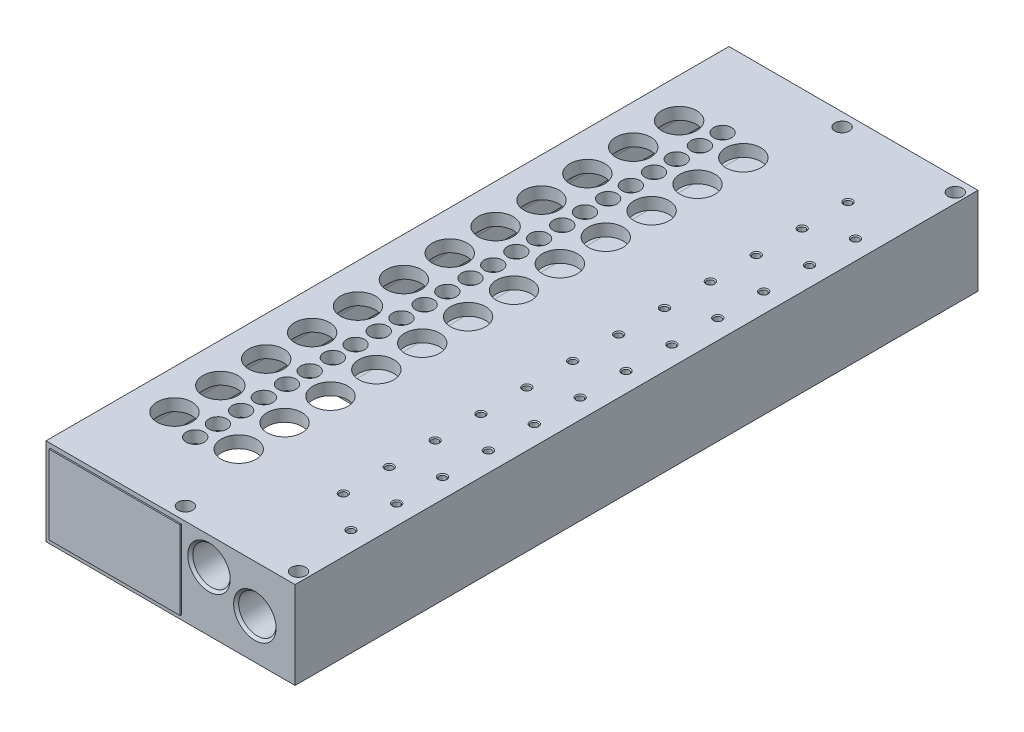
SolidWorks part; units mm, degrees
ref_plane "Front Plane" through (0, 0, 0) normal (0, 0, 1) x (1, 0, 0)
ref_plane "Top Plane" through (0, 0, 0) normal (0, 1, 0) x (1, 0, 0)
ref_plane "Right Plane" through (0, 0, 0) normal (1, 0, 0) x (0, 0, -1)
ref_plane "Plane1" through (0, 0, -135.9) normal (0, 0, 1) x (1, 0, 0)
sketch "Sketch1" plane through (0, 0, -135.9) normal (0, 0, 1) x (1, 0, 0)
  line L0 (0, 20) -> (0, 0)
  line L1 (0, 0) -> (57, 0)
  line L2 (57, 0) -> (57, 20)
  line L3 (57, 20) -> (0, 20)
  line L4 (46.9, 7.1004) -> (46.9, 8.5)
  line L5 (47.4, 9) -> (47.85, 9)
  line L6 (48.35, 9.5) -> (48.35, 11.3964)
  line L7 (38.7, 10.8091) -> (38.7, 15.1909)
  line L8 (2.5, 11.35) -> (2.5, 9.25)
  line L9 (2.5, 9.25) -> (4, 9.25)
  line L10 (4, 9.25) -> (4, 4.75)
  line L11 (6, 2.75) -> (26.7, 2.75)
  line L12 (28.7, 4.75) -> (28.7, 9.25)
  line L13 (28.7, 9.25) -> (30.2, 9.25)
  line L14 (30.2, 9.25) -> (30.2, 11.35)
  line L15 (30.2, 11.35) -> (28.7, 11.35)
  line L16 (28.7, 11.35) -> (28.7, 15.25)
  line L17 (26.7, 17.25) -> (6, 17.25)
  line L18 (4, 15.25) -> (4, 11.35)
  line L19 (4, 11.35) -> (2.5, 11.35)
  arc A0 (46.7429, 12.8926) -> (46.9, 7.1004) centre (46.95, 10) ccw
  arc A1 (46.9, 8.5) -> (47.4, 9) centre (47.4, 8.5) cw
  arc A2 (47.85, 9) -> (48.35, 9.5) centre (47.85, 9.5) ccw
  arc A3 (48.35, 11.3964) -> (46.7429, 12.8926) centre (46.85, 11.3964) ccw
  arc A4 (38.7, 15.1909) -> (38.7, 10.8091) centre (36.8, 13) ccw
  arc A5 (4, 4.75) -> (6, 2.75) centre (6, 4.75) ccw
  arc A6 (26.7, 2.75) -> (28.7, 4.75) centre (26.7, 4.75) ccw
  arc A7 (28.7, 15.25) -> (26.7, 17.25) centre (26.7, 15.25) ccw
  arc A8 (6, 17.25) -> (4, 15.25) centre (6, 15.25) ccw
extrude "Boss-Extrude1" add sketch "Sketch1" along normal blind 156.3
ref_plane "Plane2" through (0, 20, 0) normal (0, 1, 0) x (1, 0, 0)
sketch "Sketch2" plane through (0, 20, 0) normal (0, 1, 0) x (1, 0, 0)
  circle A0 centre (9, 0) radius 4
extrude "Cut-Extrude1" cut sketch "Sketch2" against normal blind 3
ref_plane "Plane3" through (0, 20, 0) normal (0, 1, 0) x (1, 0, 0)
sketch "Sketch3" plane through (0, 20, 0) normal (0, 1, 0) x (1, 0, 0)
  circle A0 centre (9, 10.5) radius 4
extrude "Cut-Extrude2" cut sketch "Sketch3" against normal blind 3
ref_plane "Plane4" through (0, 20, 0) normal (0, 1, 0) x (1, 0, 0)
sketch "Sketch4" plane through (0, 20, 0) normal (0, 1, 0) x (1, 0, 0)
  circle A0 centre (9, 21) radius 4
extrude "Cut-Extrude3" cut sketch "Sketch4" against normal blind 3
ref_plane "Plane5" through (0, 20, 0) normal (0, 1, 0) x (1, 0, 0)
sketch "Sketch5" plane through (0, 20, 0) normal (0, 1, 0) x (1, 0, 0)
  circle A0 centre (9, 31.5) radius 4
extrude "Cut-Extrude4" cut sketch "Sketch5" against normal blind 3
ref_plane "Plane6" through (0, 20, 0) normal (0, 1, 0) x (1, 0, 0)
sketch "Sketch6" plane through (0, 20, 0) normal (0, 1, 0) x (1, 0, 0)
  circle A0 centre (9, 42) radius 4
extrude "Cut-Extrude5" cut sketch "Sketch6" against normal blind 3
ref_plane "Plane7" through (0, 20, 0) normal (0, 1, 0) x (1, 0, 0)
sketch "Sketch7" plane through (0, 20, 0) normal (0, 1, 0) x (1, 0, 0)
  circle A0 centre (9, 52.5) radius 4
extrude "Cut-Extrude6" cut sketch "Sketch7" against normal blind 3
ref_plane "Plane8" through (0, 20, 0) normal (0, 1, 0) x (1, 0, 0)
sketch "Sketch8" plane through (0, 20, 0) normal (0, 1, 0) x (1, 0, 0)
  circle A0 centre (9, 63) radius 4
extrude "Cut-Extrude7" cut sketch "Sketch8" against normal blind 3
ref_plane "Plane9" through (0, 20, 0) normal (0, 1, 0) x (1, 0, 0)
sketch "Sketch9" plane through (0, 20, 0) normal (0, 1, 0) x (1, 0, 0)
  circle A0 centre (9, 73.5) radius 4
extrude "Cut-Extrude8" cut sketch "Sketch9" against normal blind 3
ref_plane "Plane10" through (0, 20, 0) normal (0, 1, 0) x (1, 0, 0)
sketch "Sketch10" plane through (0, 20, 0) normal (0, 1, 0) x (1, 0, 0)
  circle A0 centre (9, 84) radius 4
extrude "Cut-Extrude9" cut sketch "Sketch10" against normal blind 3
ref_plane "Plane11" through (0, 20, 0) normal (0, 1, 0) x (1, 0, 0)
sketch "Sketch11" plane through (0, 20, 0) normal (0, 1, 0) x (1, 0, 0)
  circle A0 centre (9, 94.5) radius 4
extrude "Cut-Extrude10" cut sketch "Sketch11" against normal blind 3
ref_plane "Plane12" through (0, 20, 0) normal (0, 1, 0) x (1, 0, 0)
sketch "Sketch12" plane through (0, 20, 0) normal (0, 1, 0) x (1, 0, 0)
  circle A0 centre (9, 105) radius 4
extrude "Cut-Extrude11" cut sketch "Sketch12" against normal blind 3
ref_plane "Plane13" through (0, 20, 0) normal (0, 1, 0) x (1, 0, 0)
sketch "Sketch13" plane through (0, 20, 0) normal (0, 1, 0) x (1, 0, 0)
  circle A0 centre (9, 115.5) radius 4
extrude "Cut-Extrude12" cut sketch "Sketch13" against normal blind 3
ref_plane "Plane14" through (0, 20, 0) normal (0, 1, 0) x (1, 0, 0)
sketch "Sketch14" plane through (0, 20, 0) normal (0, 1, 0) x (1, 0, 0)
  circle A0 centre (23.7, 0) radius 4
extrude "Cut-Extrude13" cut sketch "Sketch14" against normal blind 3
ref_plane "Plane15" through (0, 20, 0) normal (0, 1, 0) x (1, 0, 0)
sketch "Sketch15" plane through (0, 20, 0) normal (0, 1, 0) x (1, 0, 0)
  circle A0 centre (23.7, 10.5) radius 4
extrude "Cut-Extrude14" cut sketch "Sketch15" against normal blind 3
ref_plane "Plane16" through (0, 20, 0) normal (0, 1, 0) x (1, 0, 0)
sketch "Sketch16" plane through (0, 20, 0) normal (0, 1, 0) x (1, 0, 0)
  circle A0 centre (23.7, 21) radius 4
extrude "Cut-Extrude15" cut sketch "Sketch16" against normal blind 3
ref_plane "Plane17" through (0, 20, 0) normal (0, 1, 0) x (1, 0, 0)
sketch "Sketch17" plane through (0, 20, 0) normal (0, 1, 0) x (1, 0, 0)
  circle A0 centre (23.7, 31.5) radius 4
extrude "Cut-Extrude16" cut sketch "Sketch17" against normal blind 3
ref_plane "Plane18" through (0, 20, 0) normal (0, 1, 0) x (1, 0, 0)
sketch "Sketch18" plane through (0, 20, 0) normal (0, 1, 0) x (1, 0, 0)
  circle A0 centre (23.7, 42) radius 4
extrude "Cut-Extrude17" cut sketch "Sketch18" against normal blind 3
ref_plane "Plane19" through (0, 20, 0) normal (0, 1, 0) x (1, 0, 0)
sketch "Sketch19" plane through (0, 20, 0) normal (0, 1, 0) x (1, 0, 0)
  circle A0 centre (23.7, 52.5) radius 4
extrude "Cut-Extrude18" cut sketch "Sketch19" against normal blind 3
ref_plane "Plane20" through (0, 20, 0) normal (0, 1, 0) x (1, 0, 0)
sketch "Sketch20" plane through (0, 20, 0) normal (0, 1, 0) x (1, 0, 0)
  circle A0 centre (23.7, 63) radius 4
extrude "Cut-Extrude19" cut sketch "Sketch20" against normal blind 3
ref_plane "Plane21" through (0, 20, 0) normal (0, 1, 0) x (1, 0, 0)
sketch "Sketch21" plane through (0, 20, 0) normal (0, 1, 0) x (1, 0, 0)
  circle A0 centre (23.7, 73.5) radius 4
extrude "Cut-Extrude20" cut sketch "Sketch21" against normal blind 3
ref_plane "Plane22" through (0, 20, 0) normal (0, 1, 0) x (1, 0, 0)
sketch "Sketch22" plane through (0, 20, 0) normal (0, 1, 0) x (1, 0, 0)
  circle A0 centre (23.7, 84) radius 4
extrude "Cut-Extrude21" cut sketch "Sketch22" against normal blind 3
ref_plane "Plane23" through (0, 20, 0) normal (0, 1, 0) x (1, 0, 0)
sketch "Sketch23" plane through (0, 20, 0) normal (0, 1, 0) x (1, 0, 0)
  circle A0 centre (23.7, 94.5) radius 4
extrude "Cut-Extrude22" cut sketch "Sketch23" against normal blind 3
ref_plane "Plane24" through (0, 20, 0) normal (0, 1, 0) x (1, 0, 0)
sketch "Sketch24" plane through (0, 20, 0) normal (0, 1, 0) x (1, 0, 0)
  circle A0 centre (23.7, 105) radius 4
extrude "Cut-Extrude23" cut sketch "Sketch24" against normal blind 3
ref_plane "Plane25" through (0, 20, 0) normal (0, 1, 0) x (1, 0, 0)
sketch "Sketch25" plane through (0, 20, 0) normal (0, 1, 0) x (1, 0, 0)
  circle A0 centre (23.7, 115.5) radius 4
extrude "Cut-Extrude24" cut sketch "Sketch25" against normal blind 3
ref_plane "Plane26" through (0, 20, 0) normal (0, 1, 0) x (1, 0, 0)
sketch "Sketch26" plane through (0, 20, 0) normal (0, 1, 0) x (1, 0, 0)
  circle A0 centre (16.35, -2.6) radius 2.05
extrude "Cut-Extrude25" cut sketch "Sketch26" against normal blind 3
ref_plane "Plane27" through (0, 20, 0) normal (0, 1, 0) x (1, 0, 0)
sketch "Sketch27" plane through (0, 20, 0) normal (0, 1, 0) x (1, 0, 0)
  circle A0 centre (16.35, 7.9) radius 2.05
extrude "Cut-Extrude26" cut sketch "Sketch27" against normal blind 3
ref_plane "Plane28" through (0, 20, 0) normal (0, 1, 0) x (1, 0, 0)
sketch "Sketch28" plane through (0, 20, 0) normal (0, 1, 0) x (1, 0, 0)
  circle A0 centre (16.35, 18.4) radius 2.05
extrude "Cut-Extrude27" cut sketch "Sketch28" against normal blind 3
ref_plane "Plane29" through (0, 20, 0) normal (0, 1, 0) x (1, 0, 0)
sketch "Sketch29" plane through (0, 20, 0) normal (0, 1, 0) x (1, 0, 0)
  circle A0 centre (16.35, 28.9) radius 2.05
extrude "Cut-Extrude28" cut sketch "Sketch29" against normal blind 3
ref_plane "Plane30" through (0, 20, 0) normal (0, 1, 0) x (1, 0, 0)
sketch "Sketch30" plane through (0, 20, 0) normal (0, 1, 0) x (1, 0, 0)
  circle A0 centre (16.35, 39.4) radius 2.05
extrude "Cut-Extrude29" cut sketch "Sketch30" against normal blind 3
ref_plane "Plane31" through (0, 20, 0) normal (0, 1, 0) x (1, 0, 0)
sketch "Sketch31" plane through (0, 20, 0) normal (0, 1, 0) x (1, 0, 0)
  circle A0 centre (16.35, 49.9) radius 2.05
extrude "Cut-Extrude30" cut sketch "Sketch31" against normal blind 3
ref_plane "Plane32" through (0, 20, 0) normal (0, 1, 0) x (1, 0, 0)
sketch "Sketch32" plane through (0, 20, 0) normal (0, 1, 0) x (1, 0, 0)
  circle A0 centre (16.35, 60.4) radius 2.05
extrude "Cut-Extrude31" cut sketch "Sketch32" against normal blind 3
ref_plane "Plane33" through (0, 20, 0) normal (0, 1, 0) x (1, 0, 0)
sketch "Sketch33" plane through (0, 20, 0) normal (0, 1, 0) x (1, 0, 0)
  circle A0 centre (16.35, 70.9) radius 2.05
extrude "Cut-Extrude32" cut sketch "Sketch33" against normal blind 3
ref_plane "Plane34" through (0, 20, 0) normal (0, 1, 0) x (1, 0, 0)
sketch "Sketch34" plane through (0, 20, 0) normal (0, 1, 0) x (1, 0, 0)
  circle A0 centre (16.35, 81.4) radius 2.05
extrude "Cut-Extrude33" cut sketch "Sketch34" against normal blind 3
ref_plane "Plane35" through (0, 20, 0) normal (0, 1, 0) x (1, 0, 0)
sketch "Sketch35" plane through (0, 20, 0) normal (0, 1, 0) x (1, 0, 0)
  circle A0 centre (16.35, 91.9) radius 2.05
extrude "Cut-Extrude34" cut sketch "Sketch35" against normal blind 3
ref_plane "Plane36" through (0, 20, 0) normal (0, 1, 0) x (1, 0, 0)
sketch "Sketch36" plane through (0, 20, 0) normal (0, 1, 0) x (1, 0, 0)
  circle A0 centre (16.35, 102.4) radius 2.05
extrude "Cut-Extrude35" cut sketch "Sketch36" against normal blind 3
ref_plane "Plane37" through (0, 20, 0) normal (0, 1, 0) x (1, 0, 0)
sketch "Sketch37" plane through (0, 20, 0) normal (0, 1, 0) x (1, 0, 0)
  circle A0 centre (16.35, 112.9) radius 2.05
extrude "Cut-Extrude36" cut sketch "Sketch37" against normal blind 3
ref_plane "Plane38" through (0, 20, 0) normal (0, 1, 0) x (1, 0, 0)
sketch "Sketch38" plane through (0, 20, 0) normal (0, 1, 0) x (1, 0, 0)
  circle A0 centre (16.35, 2.6) radius 2.05
extrude "Cut-Extrude37" cut sketch "Sketch38" against normal blind 3
ref_plane "Plane39" through (0, 20, 0) normal (0, 1, 0) x (1, 0, 0)
sketch "Sketch39" plane through (0, 20, 0) normal (0, 1, 0) x (1, 0, 0)
  circle A0 centre (16.35, 13.1) radius 2.05
extrude "Cut-Extrude38" cut sketch "Sketch39" against normal blind 3
ref_plane "Plane40" through (0, 20, 0) normal (0, 1, 0) x (1, 0, 0)
sketch "Sketch40" plane through (0, 20, 0) normal (0, 1, 0) x (1, 0, 0)
  circle A0 centre (16.35, 23.6) radius 2.05
extrude "Cut-Extrude39" cut sketch "Sketch40" against normal blind 3
ref_plane "Plane41" through (0, 20, 0) normal (0, 1, 0) x (1, 0, 0)
sketch "Sketch41" plane through (0, 20, 0) normal (0, 1, 0) x (1, 0, 0)
  circle A0 centre (16.35, 34.1) radius 2.05
extrude "Cut-Extrude40" cut sketch "Sketch41" against normal blind 3
ref_plane "Plane42" through (0, 20, 0) normal (0, 1, 0) x (1, 0, 0)
sketch "Sketch42" plane through (0, 20, 0) normal (0, 1, 0) x (1, 0, 0)
  circle A0 centre (16.35, 44.6) radius 2.05
extrude "Cut-Extrude41" cut sketch "Sketch42" against normal blind 3
ref_plane "Plane43" through (0, 20, 0) normal (0, 1, 0) x (1, 0, 0)
sketch "Sketch43" plane through (0, 20, 0) normal (0, 1, 0) x (1, 0, 0)
  circle A0 centre (16.35, 55.1) radius 2.05
extrude "Cut-Extrude42" cut sketch "Sketch43" against normal blind 3
ref_plane "Plane44" through (0, 20, 0) normal (0, 1, 0) x (1, 0, 0)
sketch "Sketch44" plane through (0, 20, 0) normal (0, 1, 0) x (1, 0, 0)
  circle A0 centre (16.35, 65.6) radius 2.05
extrude "Cut-Extrude43" cut sketch "Sketch44" against normal blind 3
ref_plane "Plane45" through (0, 20, 0) normal (0, 1, 0) x (1, 0, 0)
sketch "Sketch45" plane through (0, 20, 0) normal (0, 1, 0) x (1, 0, 0)
  circle A0 centre (16.35, 76.1) radius 2.05
extrude "Cut-Extrude44" cut sketch "Sketch45" against normal blind 3
ref_plane "Plane46" through (0, 20, 0) normal (0, 1, 0) x (1, 0, 0)
sketch "Sketch46" plane through (0, 20, 0) normal (0, 1, 0) x (1, 0, 0)
  circle A0 centre (16.35, 86.6) radius 2.05
extrude "Cut-Extrude45" cut sketch "Sketch46" against normal blind 3
ref_plane "Plane47" through (0, 20, 0) normal (0, 1, 0) x (1, 0, 0)
sketch "Sketch47" plane through (0, 20, 0) normal (0, 1, 0) x (1, 0, 0)
  circle A0 centre (16.35, 97.1) radius 2.05
extrude "Cut-Extrude46" cut sketch "Sketch47" against normal blind 3
ref_plane "Plane48" through (0, 20, 0) normal (0, 1, 0) x (1, 0, 0)
sketch "Sketch48" plane through (0, 20, 0) normal (0, 1, 0) x (1, 0, 0)
  circle A0 centre (16.35, 107.6) radius 2.05
extrude "Cut-Extrude47" cut sketch "Sketch48" against normal blind 3
ref_plane "Plane49" through (0, 20, 0) normal (0, 1, 0) x (1, 0, 0)
sketch "Sketch49" plane through (0, 20, 0) normal (0, 1, 0) x (1, 0, 0)
  circle A0 centre (16.35, 118.1) radius 2.05
extrude "Cut-Extrude48" cut sketch "Sketch49" against normal blind 3
ref_plane "Plane50" through (44.45, 0, 0) normal (1, 0, 0) x (0, 0, -1)
sketch "Sketch50" plane through (44.45, 0, 0) normal (1, 0, 0) x (0, 0, -1)
  line L0 (3.2, 20) -> (4.2, 20)
  line L1 (4.2, 20) -> (3.9835, 19.7835)
  line L2 (3.9835, 19.7835) -> (3.9835, 14.4524)
  line L3 (3.9835, 14.4524) -> (3.2, 14)
  line L4 (3.2, 14) -> (3.2, 20)
  line L5 (3.2, 14) -> (3.2, 20) construction
revolve "Cut-Revolve1" cut sketch "Sketch50" angle 360 about L5 reverse direction yes
cosmetic thread "Cosmetic Thread1" parameters "D1"=4.5, "D2"=2
ref_plane "Plane51" through (44.45, 0, 0) normal (1, 0, 0) x (0, 0, -1)
sketch "Sketch51" plane through (44.45, 0, 0) normal (1, 0, 0) x (0, 0, -1)
  line L0 (13.7, 20) -> (14.7, 20)
  line L1 (14.7, 20) -> (14.4835, 19.7835)
  line L2 (14.4835, 19.7835) -> (14.4835, 14.4524)
  line L3 (14.4835, 14.4524) -> (13.7, 14)
  line L4 (13.7, 14) -> (13.7, 20)
  line L5 (13.7, 14) -> (13.7, 20) construction
revolve "Cut-Revolve2" cut sketch "Sketch51" angle 360 about L5 reverse direction yes
cosmetic thread "Cosmetic Thread2" parameters "D1"=4.5, "D2"=2
ref_plane "Plane52" through (44.45, 0, 0) normal (1, 0, 0) x (0, 0, -1)
sketch "Sketch52" plane through (44.45, 0, 0) normal (1, 0, 0) x (0, 0, -1)
  line L0 (24.2, 20) -> (25.2, 20)
  line L1 (25.2, 20) -> (24.9835, 19.7835)
  line L2 (24.9835, 19.7835) -> (24.9835, 14.4524)
  line L3 (24.9835, 14.4524) -> (24.2, 14)
  line L4 (24.2, 14) -> (24.2, 20)
  line L5 (24.2, 14) -> (24.2, 20) construction
revolve "Cut-Revolve3" cut sketch "Sketch52" angle 360 about L5 reverse direction yes
cosmetic thread "Cosmetic Thread3" parameters "D1"=4.5, "D2"=2
ref_plane "Plane53" through (44.45, 0, 0) normal (1, 0, 0) x (0, 0, -1)
sketch "Sketch53" plane through (44.45, 0, 0) normal (1, 0, 0) x (0, 0, -1)
  line L0 (34.7, 20) -> (35.7, 20)
  line L1 (35.7, 20) -> (35.4835, 19.7835)
  line L2 (35.4835, 19.7835) -> (35.4835, 14.4524)
  line L3 (35.4835, 14.4524) -> (34.7, 14)
  line L4 (34.7, 14) -> (34.7, 20)
  line L5 (34.7, 14) -> (34.7, 20) construction
revolve "Cut-Revolve4" cut sketch "Sketch53" angle 360 about L5 reverse direction yes
cosmetic thread "Cosmetic Thread4" parameters "D1"=4.5, "D2"=2
ref_plane "Plane54" through (44.45, 0, 0) normal (1, 0, 0) x (0, 0, -1)
sketch "Sketch54" plane through (44.45, 0, 0) normal (1, 0, 0) x (0, 0, -1)
  line L0 (45.2, 20) -> (46.2, 20)
  line L1 (46.2, 20) -> (45.9835, 19.7835)
  line L2 (45.9835, 19.7835) -> (45.9835, 14.4524)
  line L3 (45.9835, 14.4524) -> (45.2, 14)
  line L4 (45.2, 14) -> (45.2, 20)
  line L5 (45.2, 14) -> (45.2, 20) construction
revolve "Cut-Revolve5" cut sketch "Sketch54" angle 360 about L5 reverse direction yes
cosmetic thread "Cosmetic Thread5" parameters "D1"=4.5, "D2"=2
ref_plane "Plane55" through (44.45, 0, 0) normal (1, 0, 0) x (0, 0, -1)
sketch "Sketch55" plane through (44.45, 0, 0) normal (1, 0, 0) x (0, 0, -1)
  line L0 (55.7, 20) -> (56.7, 20)
  line L1 (56.7, 20) -> (56.4835, 19.7835)
  line L2 (56.4835, 19.7835) -> (56.4835, 14.4524)
  line L3 (56.4835, 14.4524) -> (55.7, 14)
  line L4 (55.7, 14) -> (55.7, 20)
  line L5 (55.7, 14) -> (55.7, 20) construction
revolve "Cut-Revolve6" cut sketch "Sketch55" angle 360 about L5 reverse direction yes
cosmetic thread "Cosmetic Thread6" parameters "D1"=4.5, "D2"=2
ref_plane "Plane56" through (44.45, 0, 0) normal (1, 0, 0) x (0, 0, -1)
sketch "Sketch56" plane through (44.45, 0, 0) normal (1, 0, 0) x (0, 0, -1)
  line L0 (66.2, 20) -> (67.2, 20)
  line L1 (67.2, 20) -> (66.9835, 19.7835)
  line L2 (66.9835, 19.7835) -> (66.9835, 14.4524)
  line L3 (66.9835, 14.4524) -> (66.2, 14)
  line L4 (66.2, 14) -> (66.2, 20)
  line L5 (66.2, 14) -> (66.2, 20) construction
revolve "Cut-Revolve7" cut sketch "Sketch56" angle 360 about L5 reverse direction yes
cosmetic thread "Cosmetic Thread7" parameters "D1"=4.5, "D2"=2
ref_plane "Plane57" through (44.45, 0, 0) normal (1, 0, 0) x (0, 0, -1)
sketch "Sketch57" plane through (44.45, 0, 0) normal (1, 0, 0) x (0, 0, -1)
  line L0 (76.7, 20) -> (77.7, 20)
  line L1 (77.7, 20) -> (77.4835, 19.7835)
  line L2 (77.4835, 19.7835) -> (77.4835, 14.4524)
  line L3 (77.4835, 14.4524) -> (76.7, 14)
  line L4 (76.7, 14) -> (76.7, 20)
  line L5 (76.7, 14) -> (76.7, 20) construction
revolve "Cut-Revolve8" cut sketch "Sketch57" angle 360 about L5 reverse direction yes
cosmetic thread "Cosmetic Thread8" parameters "D1"=4.5, "D2"=2
ref_plane "Plane58" through (44.45, 0, 0) normal (1, 0, 0) x (0, 0, -1)
sketch "Sketch58" plane through (44.45, 0, 0) normal (1, 0, 0) x (0, 0, -1)
  line L0 (87.2, 20) -> (88.2, 20)
  line L1 (88.2, 20) -> (87.9835, 19.7835)
  line L2 (87.9835, 19.7835) -> (87.9835, 14.4524)
  line L3 (87.9835, 14.4524) -> (87.2, 14)
  line L4 (87.2, 14) -> (87.2, 20)
  line L5 (87.2, 14) -> (87.2, 20) construction
revolve "Cut-Revolve9" cut sketch "Sketch58" angle 360 about L5 reverse direction yes
cosmetic thread "Cosmetic Thread9" parameters "D1"=4.5, "D2"=2
ref_plane "Plane59" through (44.45, 0, 0) normal (1, 0, 0) x (0, 0, -1)
sketch "Sketch59" plane through (44.45, 0, 0) normal (1, 0, 0) x (0, 0, -1)
  line L0 (97.7, 20) -> (98.7, 20)
  line L1 (98.7, 20) -> (98.4835, 19.7835)
  line L2 (98.4835, 19.7835) -> (98.4835, 14.4524)
  line L3 (98.4835, 14.4524) -> (97.7, 14)
  line L4 (97.7, 14) -> (97.7, 20)
  line L5 (97.7, 14) -> (97.7, 20) construction
revolve "Cut-Revolve10" cut sketch "Sketch59" angle 360 about L5 reverse direction yes
cosmetic thread "Cosmetic Thread10" parameters "D1"=4.5, "D2"=2
ref_plane "Plane60" through (44.45, 0, 0) normal (1, 0, 0) x (0, 0, -1)
sketch "Sketch60" plane through (44.45, 0, 0) normal (1, 0, 0) x (0, 0, -1)
  line L0 (108.2, 20) -> (109.2, 20)
  line L1 (109.2, 20) -> (108.9835, 19.7835)
  line L2 (108.9835, 19.7835) -> (108.9835, 14.4524)
  line L3 (108.9835, 14.4524) -> (108.2, 14)
  line L4 (108.2, 14) -> (108.2, 20)
  line L5 (108.2, 14) -> (108.2, 20) construction
revolve "Cut-Revolve11" cut sketch "Sketch60" angle 360 about L5 reverse direction yes
cosmetic thread "Cosmetic Thread11" parameters "D1"=4.5, "D2"=2
ref_plane "Plane61" through (44.45, 0, 0) normal (1, 0, 0) x (0, 0, -1)
sketch "Sketch61" plane through (44.45, 0, 0) normal (1, 0, 0) x (0, 0, -1)
  line L0 (118.7, 20) -> (119.7, 20)
  line L1 (119.7, 20) -> (119.4835, 19.7835)
  line L2 (119.4835, 19.7835) -> (119.4835, 14.4524)
  line L3 (119.4835, 14.4524) -> (118.7, 14)
  line L4 (118.7, 14) -> (118.7, 20)
  line L5 (118.7, 14) -> (118.7, 20) construction
revolve "Cut-Revolve12" cut sketch "Sketch61" angle 360 about L5 reverse direction yes
cosmetic thread "Cosmetic Thread12" parameters "D1"=4.5, "D2"=2
ref_plane "Plane62" through (52.6, 0, 0) normal (1, 0, 0) x (0, 0, -1)
sketch "Sketch62" plane through (52.6, 0, 0) normal (1, 0, 0) x (0, 0, -1)
  line L0 (-3.2, 20) -> (-2.2, 20)
  line L1 (-2.2, 20) -> (-2.4165, 19.7835)
  line L2 (-2.4165, 19.7835) -> (-2.4165, 14.4524)
  line L3 (-2.4165, 14.4524) -> (-3.2, 14)
  line L4 (-3.2, 14) -> (-3.2, 20)
  line L5 (-3.2, 14) -> (-3.2, 20) construction
revolve "Cut-Revolve13" cut sketch "Sketch62" angle 360 about L5 reverse direction yes
cosmetic thread "Cosmetic Thread13" parameters "D1"=4.5, "D2"=2
ref_plane "Plane63" through (52.55, 0, 0) normal (1, 0, 0) x (0, 0, -1)
sketch "Sketch63" plane through (52.55, 0, 0) normal (1, 0, 0) x (0, 0, -1)
  line L0 (7.3, 20) -> (8.3, 20)
  line L1 (8.3, 20) -> (8.0835, 19.7835)
  line L2 (8.0835, 19.7835) -> (8.0835, 14.4524)
  line L3 (8.0835, 14.4524) -> (7.3, 14)
  line L4 (7.3, 14) -> (7.3, 20)
  line L5 (7.3, 14) -> (7.3, 20) construction
revolve "Cut-Revolve14" cut sketch "Sketch63" angle 360 about L5 reverse direction yes
cosmetic thread "Cosmetic Thread14" parameters "D1"=4.5, "D2"=2
ref_plane "Plane64" through (52.55, 0, 0) normal (1, 0, 0) x (0, 0, -1)
sketch "Sketch64" plane through (52.55, 0, 0) normal (1, 0, 0) x (0, 0, -1)
  line L0 (17.8, 20) -> (18.8, 20)
  line L1 (18.8, 20) -> (18.5835, 19.7835)
  line L2 (18.5835, 19.7835) -> (18.5835, 14.4524)
  line L3 (18.5835, 14.4524) -> (17.8, 14)
  line L4 (17.8, 14) -> (17.8, 20)
  line L5 (17.8, 14) -> (17.8, 20) construction
revolve "Cut-Revolve15" cut sketch "Sketch64" angle 360 about L5 reverse direction yes
cosmetic thread "Cosmetic Thread15" parameters "D1"=4.5, "D2"=2
ref_plane "Plane65" through (52.55, 0, 0) normal (1, 0, 0) x (0, 0, -1)
sketch "Sketch65" plane through (52.55, 0, 0) normal (1, 0, 0) x (0, 0, -1)
  line L0 (28.3, 20) -> (29.3, 20)
  line L1 (29.3, 20) -> (29.0835, 19.7835)
  line L2 (29.0835, 19.7835) -> (29.0835, 14.4524)
  line L3 (29.0835, 14.4524) -> (28.3, 14)
  line L4 (28.3, 14) -> (28.3, 20)
  line L5 (28.3, 14) -> (28.3, 20) construction
revolve "Cut-Revolve16" cut sketch "Sketch65" angle 360 about L5 reverse direction yes
cosmetic thread "Cosmetic Thread16" parameters "D1"=4.5, "D2"=2
ref_plane "Plane66" through (52.55, 0, 0) normal (1, 0, 0) x (0, 0, -1)
sketch "Sketch66" plane through (52.55, 0, 0) normal (1, 0, 0) x (0, 0, -1)
  line L0 (38.8, 20) -> (39.8, 20)
  line L1 (39.8, 20) -> (39.5835, 19.7835)
  line L2 (39.5835, 19.7835) -> (39.5835, 14.4524)
  line L3 (39.5835, 14.4524) -> (38.8, 14)
  line L4 (38.8, 14) -> (38.8, 20)
  line L5 (38.8, 14) -> (38.8, 20) construction
revolve "Cut-Revolve17" cut sketch "Sketch66" angle 360 about L5 reverse direction yes
cosmetic thread "Cosmetic Thread17" parameters "D1"=4.5, "D2"=2
ref_plane "Plane67" through (52.55, 0, 0) normal (1, 0, 0) x (0, 0, -1)
sketch "Sketch67" plane through (52.55, 0, 0) normal (1, 0, 0) x (0, 0, -1)
  line L0 (49.3, 20) -> (50.3, 20)
  line L1 (50.3, 20) -> (50.0835, 19.7835)
  line L2 (50.0835, 19.7835) -> (50.0835, 14.4524)
  line L3 (50.0835, 14.4524) -> (49.3, 14)
  line L4 (49.3, 14) -> (49.3, 20)
  line L5 (49.3, 14) -> (49.3, 20) construction
revolve "Cut-Revolve18" cut sketch "Sketch67" angle 360 about L5 reverse direction yes
cosmetic thread "Cosmetic Thread18" parameters "D1"=4.5, "D2"=2
ref_plane "Plane68" through (52.55, 0, 0) normal (1, 0, 0) x (0, 0, -1)
sketch "Sketch68" plane through (52.55, 0, 0) normal (1, 0, 0) x (0, 0, -1)
  line L0 (59.8, 20) -> (60.8, 20)
  line L1 (60.8, 20) -> (60.5835, 19.7835)
  line L2 (60.5835, 19.7835) -> (60.5835, 14.4524)
  line L3 (60.5835, 14.4524) -> (59.8, 14)
  line L4 (59.8, 14) -> (59.8, 20)
  line L5 (59.8, 14) -> (59.8, 20) construction
revolve "Cut-Revolve19" cut sketch "Sketch68" angle 360 about L5 reverse direction yes
cosmetic thread "Cosmetic Thread19" parameters "D1"=4.5, "D2"=2
ref_plane "Plane69" through (52.55, 0, 0) normal (1, 0, 0) x (0, 0, -1)
sketch "Sketch69" plane through (52.55, 0, 0) normal (1, 0, 0) x (0, 0, -1)
  line L0 (70.3, 20) -> (71.3, 20)
  line L1 (71.3, 20) -> (71.0835, 19.7835)
  line L2 (71.0835, 19.7835) -> (71.0835, 14.4524)
  line L3 (71.0835, 14.4524) -> (70.3, 14)
  line L4 (70.3, 14) -> (70.3, 20)
  line L5 (70.3, 14) -> (70.3, 20) construction
revolve "Cut-Revolve20" cut sketch "Sketch69" angle 360 about L5 reverse direction yes
cosmetic thread "Cosmetic Thread20" parameters "D1"=4.5, "D2"=2
ref_plane "Plane70" through (52.55, 0, 0) normal (1, 0, 0) x (0, 0, -1)
sketch "Sketch70" plane through (52.55, 0, 0) normal (1, 0, 0) x (0, 0, -1)
  line L0 (80.8, 20) -> (81.8, 20)
  line L1 (81.8, 20) -> (81.5835, 19.7835)
  line L2 (81.5835, 19.7835) -> (81.5835, 14.4524)
  line L3 (81.5835, 14.4524) -> (80.8, 14)
  line L4 (80.8, 14) -> (80.8, 20)
  line L5 (80.8, 14) -> (80.8, 20) construction
revolve "Cut-Revolve21" cut sketch "Sketch70" angle 360 about L5 reverse direction yes
cosmetic thread "Cosmetic Thread21" parameters "D1"=4.5, "D2"=2
ref_plane "Plane71" through (52.55, 0, 0) normal (1, 0, 0) x (0, 0, -1)
sketch "Sketch71" plane through (52.55, 0, 0) normal (1, 0, 0) x (0, 0, -1)
  line L0 (91.3, 20) -> (92.3, 20)
  line L1 (92.3, 20) -> (92.0835, 19.7835)
  line L2 (92.0835, 19.7835) -> (92.0835, 14.4524)
  line L3 (92.0835, 14.4524) -> (91.3, 14)
  line L4 (91.3, 14) -> (91.3, 20)
  line L5 (91.3, 14) -> (91.3, 20) construction
revolve "Cut-Revolve22" cut sketch "Sketch71" angle 360 about L5 reverse direction yes
cosmetic thread "Cosmetic Thread22" parameters "D1"=4.5, "D2"=2
ref_plane "Plane72" through (52.55, 0, 0) normal (1, 0, 0) x (0, 0, -1)
sketch "Sketch72" plane through (52.55, 0, 0) normal (1, 0, 0) x (0, 0, -1)
  line L0 (101.8, 20) -> (102.8, 20)
  line L1 (102.8, 20) -> (102.5835, 19.7835)
  line L2 (102.5835, 19.7835) -> (102.5835, 14.4524)
  line L3 (102.5835, 14.4524) -> (101.8, 14)
  line L4 (101.8, 14) -> (101.8, 20)
  line L5 (101.8, 14) -> (101.8, 20) construction
revolve "Cut-Revolve23" cut sketch "Sketch72" angle 360 about L5 reverse direction yes
cosmetic thread "Cosmetic Thread23" parameters "D1"=4.5, "D2"=2
ref_plane "Plane73" through (52.55, 0, 0) normal (1, 0, 0) x (0, 0, -1)
sketch "Sketch73" plane through (52.55, 0, 0) normal (1, 0, 0) x (0, 0, -1)
  line L0 (112.3, 20) -> (113.3, 20)
  line L1 (113.3, 20) -> (113.0835, 19.7835)
  line L2 (113.0835, 19.7835) -> (113.0835, 14.4524)
  line L3 (113.0835, 14.4524) -> (112.3, 14)
  line L4 (112.3, 14) -> (112.3, 20)
  line L5 (112.3, 14) -> (112.3, 20) construction
revolve "Cut-Revolve24" cut sketch "Sketch73" angle 360 about L5 reverse direction yes
cosmetic thread "Cosmetic Thread24" parameters "D1"=4.5, "D2"=2
ref_plane "Plane74" through (37.3, 0, 0) normal (1, 0, 0) x (0, 0, -1)
sketch "Sketch74" plane through (37.3, 0, 0) normal (1, 0, 0) x (0, 0, -1)
  line L0 (-20.4, 13.6) -> (-20.4, 18.464)
  line L1 (-20.4, 18.464) -> (-19.819, 17.883)
  line L2 (-19.819, 17.883) -> (-9.4, 17.883)
  line L3 (-9.4, 17.883) -> (-9.4, 13.6)
  line L4 (-9.4, 13.6) -> (-20.4, 13.6)
  line L5 (-9.4, 13.6) -> (-20.4, 13.6) construction
revolve "Cut-Revolve25" cut sketch "Sketch74" angle 360 about L5 reverse direction yes
cosmetic thread "Cosmetic Thread25" parameters "D1"=8, "D2"=9.728
ref_plane "Plane75" through (37.3, 0, 0) normal (1, 0, 0) x (0, 0, -1)
sketch "Sketch75" plane through (37.3, 0, 0) normal (1, 0, 0) x (0, 0, -1)
  line L0 (124.9, 13.6) -> (124.9, 17.883)
  line L1 (124.9, 17.883) -> (135.319, 17.883)
  line L2 (135.319, 17.883) -> (135.9, 18.464)
  line L3 (135.9, 18.464) -> (135.9, 13.6)
  line L4 (135.9, 13.6) -> (124.9, 13.6)
  line L5 (135.9, 13.6) -> (124.9, 13.6) construction
revolve "Cut-Revolve26" cut sketch "Sketch75" angle 360 about L5 reverse direction yes
cosmetic thread "Cosmetic Thread26" parameters "D1"=8, "D2"=9.728
ref_plane "Plane76" through (47.8, 0, 0) normal (1, 0, 0) x (0, 0, -1)
sketch "Sketch76" plane through (47.8, 0, 0) normal (1, 0, 0) x (0, 0, -1)
  line L0 (-20.4, 9.2) -> (-20.4, 14.064)
  line L1 (-20.4, 14.064) -> (-19.819, 13.483)
  line L2 (-19.819, 13.483) -> (-9.4, 13.483)
  line L3 (-9.4, 13.483) -> (-9.4, 9.2)
  line L4 (-9.4, 9.2) -> (-20.4, 9.2)
  line L5 (-9.4, 9.2) -> (-20.4, 9.2) construction
revolve "Cut-Revolve27" cut sketch "Sketch76" angle 360 about L5 reverse direction yes
cosmetic thread "Cosmetic Thread27" parameters "D1"=8, "D2"=9.728
ref_plane "Plane77" through (47.8, 0, 0) normal (1, 0, 0) x (0, 0, -1)
sketch "Sketch77" plane through (47.8, 0, 0) normal (1, 0, 0) x (0, 0, -1)
  line L0 (124.9, 9.2) -> (124.9, 13.483)
  line L1 (124.9, 13.483) -> (135.319, 13.483)
  line L2 (135.319, 13.483) -> (135.9, 14.064)
  line L3 (135.9, 14.064) -> (135.9, 9.2)
  line L4 (135.9, 9.2) -> (124.9, 9.2)
  line L5 (135.9, 9.2) -> (124.9, 9.2) construction
revolve "Cut-Revolve28" cut sketch "Sketch77" angle 360 about L5 reverse direction yes
cosmetic thread "Cosmetic Thread28" parameters "D1"=8, "D2"=9.728
ref_plane "Plane78" through (0, 0, 17.4) normal (0, 0, 1) x (1, 0, 0)
sketch "Sketch78" plane through (0, 0, 17.4) normal (0, 0, 1) x (1, 0, 0)
  line L0 (54.8, 20) -> (56.45, 20)
  line L1 (56.45, 20) -> (56.45, 0)
  line L2 (56.45, 0) -> (54.8, 0)
  line L3 (54.8, 0) -> (54.8, 20)
  line L4 (54.8, 0) -> (54.8, 20) construction
revolve "Cut-Revolve29" cut sketch "Sketch78" angle 360 about L4 reverse direction yes
ref_plane "Plane79" through (0, 0, 17.4) normal (0, 0, 1) x (1, 0, 0)
sketch "Sketch79" plane through (0, 0, 17.4) normal (0, 0, 1) x (1, 0, 0)
  line L0 (28.9, 20) -> (30.55, 20)
  line L1 (30.55, 20) -> (30.55, 0)
  line L2 (30.55, 0) -> (28.9, 0)
  line L3 (28.9, 0) -> (28.9, 20)
  line L4 (28.9, 0) -> (28.9, 20) construction
revolve "Cut-Revolve30" cut sketch "Sketch79" angle 360 about L4 reverse direction yes
ref_plane "Plane80" through (0, 0, -132.9) normal (0, 0, 1) x (1, 0, 0)
sketch "Sketch80" plane through (0, 0, -132.9) normal (0, 0, 1) x (1, 0, 0)
  line L0 (54.8, 20) -> (56.45, 20)
  line L1 (56.45, 20) -> (56.45, 0)
  line L2 (56.45, 0) -> (54.8, 0)
  line L3 (54.8, 0) -> (54.8, 20)
  line L4 (54.8, 0) -> (54.8, 20) construction
revolve "Cut-Revolve31" cut sketch "Sketch80" angle 360 about L4 reverse direction yes
ref_plane "Plane81" through (0, 0, -132.9) normal (0, 0, 1) x (1, 0, 0)
sketch "Sketch81" plane through (0, 0, -132.9) normal (0, 0, 1) x (1, 0, 0)
  line L0 (28.9, 20) -> (30.55, 20)
  line L1 (30.55, 20) -> (30.55, 0)
  line L2 (30.55, 0) -> (28.9, 0)
  line L3 (28.9, 0) -> (28.9, 20)
  line L4 (28.9, 0) -> (28.9, 20) construction
revolve "Cut-Revolve32" cut sketch "Sketch81" angle 360 about L4 reverse direction yes
ref_plane "Plane82" through (0, 0, 2.5) normal (0, 0, 1) x (1, 0, 0)
sketch "Sketch82" plane through (0, 0, 2.5) normal (0, 0, 1) x (1, 0, 0)
  line L0 (40.4, 7.2) -> (42.467, 7.2)
  line L1 (42.467, 7.2) -> (42.467, 0.433)
  line L2 (42.467, 0.433) -> (42.9, 0)
  line L3 (42.9, 0) -> (40.4, 0)
  line L4 (40.4, 0) -> (40.4, 7.2)
  line L5 (40.4, 0) -> (40.4, 7.2) construction
revolve "Cut-Revolve33" cut sketch "Sketch82" angle 360 about L5 reverse direction yes
cosmetic thread "Cosmetic Thread29" parameters "D1"=4.8, "D2"=5
ref_plane "Plane83" through (0, 0, -8) normal (0, 0, 1) x (1, 0, 0)
sketch "Sketch83" plane through (0, 0, -8) normal (0, 0, 1) x (1, 0, 0)
  line L0 (40.4, 7.2) -> (42.467, 7.2)
  line L1 (42.467, 7.2) -> (42.467, 0.433)
  line L2 (42.467, 0.433) -> (42.9, 0)
  line L3 (42.9, 0) -> (40.4, 0)
  line L4 (40.4, 0) -> (40.4, 7.2)
  line L5 (40.4, 0) -> (40.4, 7.2) construction
revolve "Cut-Revolve34" cut sketch "Sketch83" angle 360 about L5 reverse direction yes
cosmetic thread "Cosmetic Thread30" parameters "D1"=4.8, "D2"=5
ref_plane "Plane84" through (0, 0, -18.5) normal (0, 0, 1) x (1, 0, 0)
sketch "Sketch84" plane through (0, 0, -18.5) normal (0, 0, 1) x (1, 0, 0)
  line L0 (40.4, 7.2) -> (42.467, 7.2)
  line L1 (42.467, 7.2) -> (42.467, 0.433)
  line L2 (42.467, 0.433) -> (42.9, 0)
  line L3 (42.9, 0) -> (40.4, 0)
  line L4 (40.4, 0) -> (40.4, 7.2)
  line L5 (40.4, 0) -> (40.4, 7.2) construction
revolve "Cut-Revolve35" cut sketch "Sketch84" angle 360 about L5 reverse direction yes
cosmetic thread "Cosmetic Thread31" parameters "D1"=4.8, "D2"=5
ref_plane "Plane85" through (0, 0, -29) normal (0, 0, 1) x (1, 0, 0)
sketch "Sketch85" plane through (0, 0, -29) normal (0, 0, 1) x (1, 0, 0)
  line L0 (40.4, 7.2) -> (42.467, 7.2)
  line L1 (42.467, 7.2) -> (42.467, 0.433)
  line L2 (42.467, 0.433) -> (42.9, 0)
  line L3 (42.9, 0) -> (40.4, 0)
  line L4 (40.4, 0) -> (40.4, 7.2)
  line L5 (40.4, 0) -> (40.4, 7.2) construction
revolve "Cut-Revolve36" cut sketch "Sketch85" angle 360 about L5 reverse direction yes
cosmetic thread "Cosmetic Thread32" parameters "D1"=4.8, "D2"=5
ref_plane "Plane86" through (0, 0, -39.5) normal (0, 0, 1) x (1, 0, 0)
sketch "Sketch86" plane through (0, 0, -39.5) normal (0, 0, 1) x (1, 0, 0)
  line L0 (40.4, 7.2) -> (42.467, 7.2)
  line L1 (42.467, 7.2) -> (42.467, 0.433)
  line L2 (42.467, 0.433) -> (42.9, 0)
  line L3 (42.9, 0) -> (40.4, 0)
  line L4 (40.4, 0) -> (40.4, 7.2)
  line L5 (40.4, 0) -> (40.4, 7.2) construction
revolve "Cut-Revolve37" cut sketch "Sketch86" angle 360 about L5 reverse direction yes
cosmetic thread "Cosmetic Thread33" parameters "D1"=4.8, "D2"=5
ref_plane "Plane87" through (0, 0, -50) normal (0, 0, 1) x (1, 0, 0)
sketch "Sketch87" plane through (0, 0, -50) normal (0, 0, 1) x (1, 0, 0)
  line L0 (40.4, 7.2) -> (42.467, 7.2)
  line L1 (42.467, 7.2) -> (42.467, 0.433)
  line L2 (42.467, 0.433) -> (42.9, 0)
  line L3 (42.9, 0) -> (40.4, 0)
  line L4 (40.4, 0) -> (40.4, 7.2)
  line L5 (40.4, 0) -> (40.4, 7.2) construction
revolve "Cut-Revolve38" cut sketch "Sketch87" angle 360 about L5 reverse direction yes
cosmetic thread "Cosmetic Thread34" parameters "D1"=4.8, "D2"=5
ref_plane "Plane88" through (0, 0, -60.5) normal (0, 0, 1) x (1, 0, 0)
sketch "Sketch88" plane through (0, 0, -60.5) normal (0, 0, 1) x (1, 0, 0)
  line L0 (40.4, 7.2) -> (42.467, 7.2)
  line L1 (42.467, 7.2) -> (42.467, 0.433)
  line L2 (42.467, 0.433) -> (42.9, 0)
  line L3 (42.9, 0) -> (40.4, 0)
  line L4 (40.4, 0) -> (40.4, 7.2)
  line L5 (40.4, 0) -> (40.4, 7.2) construction
revolve "Cut-Revolve39" cut sketch "Sketch88" angle 360 about L5 reverse direction yes
cosmetic thread "Cosmetic Thread35" parameters "D1"=4.8, "D2"=5
ref_plane "Plane89" through (0, 0, -71) normal (0, 0, 1) x (1, 0, 0)
sketch "Sketch89" plane through (0, 0, -71) normal (0, 0, 1) x (1, 0, 0)
  line L0 (40.4, 7.2) -> (42.467, 7.2)
  line L1 (42.467, 7.2) -> (42.467, 0.433)
  line L2 (42.467, 0.433) -> (42.9, 0)
  line L3 (42.9, 0) -> (40.4, 0)
  line L4 (40.4, 0) -> (40.4, 7.2)
  line L5 (40.4, 0) -> (40.4, 7.2) construction
revolve "Cut-Revolve40" cut sketch "Sketch89" angle 360 about L5 reverse direction yes
cosmetic thread "Cosmetic Thread36" parameters "D1"=4.8, "D2"=5
ref_plane "Plane90" through (0, 0, -81.5) normal (0, 0, 1) x (1, 0, 0)
sketch "Sketch90" plane through (0, 0, -81.5) normal (0, 0, 1) x (1, 0, 0)
  line L0 (40.4, 7.2) -> (42.467, 7.2)
  line L1 (42.467, 7.2) -> (42.467, 0.433)
  line L2 (42.467, 0.433) -> (42.9, 0)
  line L3 (42.9, 0) -> (40.4, 0)
  line L4 (40.4, 0) -> (40.4, 7.2)
  line L5 (40.4, 0) -> (40.4, 7.2) construction
revolve "Cut-Revolve41" cut sketch "Sketch90" angle 360 about L5 reverse direction yes
cosmetic thread "Cosmetic Thread37" parameters "D1"=4.8, "D2"=5
ref_plane "Plane91" through (0, 0, -92) normal (0, 0, 1) x (1, 0, 0)
sketch "Sketch91" plane through (0, 0, -92) normal (0, 0, 1) x (1, 0, 0)
  line L0 (40.4, 7.2) -> (42.467, 7.2)
  line L1 (42.467, 7.2) -> (42.467, 0.433)
  line L2 (42.467, 0.433) -> (42.9, 0)
  line L3 (42.9, 0) -> (40.4, 0)
  line L4 (40.4, 0) -> (40.4, 7.2)
  line L5 (40.4, 0) -> (40.4, 7.2) construction
revolve "Cut-Revolve42" cut sketch "Sketch91" angle 360 about L5 reverse direction yes
cosmetic thread "Cosmetic Thread38" parameters "D1"=4.8, "D2"=5
ref_plane "Plane92" through (0, 0, -102.5) normal (0, 0, 1) x (1, 0, 0)
sketch "Sketch92" plane through (0, 0, -102.5) normal (0, 0, 1) x (1, 0, 0)
  line L0 (40.4, 7.2) -> (42.467, 7.2)
  line L1 (42.467, 7.2) -> (42.467, 0.433)
  line L2 (42.467, 0.433) -> (42.9, 0)
  line L3 (42.9, 0) -> (40.4, 0)
  line L4 (40.4, 0) -> (40.4, 7.2)
  line L5 (40.4, 0) -> (40.4, 7.2) construction
revolve "Cut-Revolve43" cut sketch "Sketch92" angle 360 about L5 reverse direction yes
cosmetic thread "Cosmetic Thread39" parameters "D1"=4.8, "D2"=5
ref_plane "Plane93" through (0, 0, -113) normal (0, 0, 1) x (1, 0, 0)
sketch "Sketch93" plane through (0, 0, -113) normal (0, 0, 1) x (1, 0, 0)
  line L0 (40.4, 7.2) -> (42.467, 7.2)
  line L1 (42.467, 7.2) -> (42.467, 0.433)
  line L2 (42.467, 0.433) -> (42.9, 0)
  line L3 (42.9, 0) -> (40.4, 0)
  line L4 (40.4, 0) -> (40.4, 7.2)
  line L5 (40.4, 0) -> (40.4, 7.2) construction
revolve "Cut-Revolve44" cut sketch "Sketch93" angle 360 about L5 reverse direction yes
cosmetic thread "Cosmetic Thread40" parameters "D1"=4.8, "D2"=5
ref_plane "Plane94" through (0, 0, -2.4) normal (0, 0, 1) x (1, 0, 0)
sketch "Sketch94" plane through (0, 0, -2.4) normal (0, 0, 1) x (1, 0, 0)
  line L0 (49.3, 7.2) -> (51.367, 7.2)
  line L1 (51.367, 7.2) -> (51.367, 0.433)
  line L2 (51.367, 0.433) -> (51.8, 0)
  line L3 (51.8, 0) -> (49.3, 0)
  line L4 (49.3, 0) -> (49.3, 7.2)
  line L5 (49.3, 0) -> (49.3, 7.2) construction
revolve "Cut-Revolve45" cut sketch "Sketch94" angle 360 about L5 reverse direction yes
cosmetic thread "Cosmetic Thread41" parameters "D1"=4.8, "D2"=5
ref_plane "Plane95" through (0, 0, -12.9) normal (0, 0, 1) x (1, 0, 0)
sketch "Sketch95" plane through (0, 0, -12.9) normal (0, 0, 1) x (1, 0, 0)
  line L0 (49.3, 7.2) -> (51.367, 7.2)
  line L1 (51.367, 7.2) -> (51.367, 0.433)
  line L2 (51.367, 0.433) -> (51.8, 0)
  line L3 (51.8, 0) -> (49.3, 0)
  line L4 (49.3, 0) -> (49.3, 7.2)
  line L5 (49.3, 0) -> (49.3, 7.2) construction
revolve "Cut-Revolve46" cut sketch "Sketch95" angle 360 about L5 reverse direction yes
cosmetic thread "Cosmetic Thread42" parameters "D1"=4.8, "D2"=5
ref_plane "Plane96" through (0, 0, -23.4) normal (0, 0, 1) x (1, 0, 0)
sketch "Sketch96" plane through (0, 0, -23.4) normal (0, 0, 1) x (1, 0, 0)
  line L0 (49.3, 7.2) -> (51.367, 7.2)
  line L1 (51.367, 7.2) -> (51.367, 0.433)
  line L2 (51.367, 0.433) -> (51.8, 0)
  line L3 (51.8, 0) -> (49.3, 0)
  line L4 (49.3, 0) -> (49.3, 7.2)
  line L5 (49.3, 0) -> (49.3, 7.2) construction
revolve "Cut-Revolve47" cut sketch "Sketch96" angle 360 about L5 reverse direction yes
cosmetic thread "Cosmetic Thread43" parameters "D1"=4.8, "D2"=5
ref_plane "Plane97" through (0, 0, -33.9) normal (0, 0, 1) x (1, 0, 0)
sketch "Sketch97" plane through (0, 0, -33.9) normal (0, 0, 1) x (1, 0, 0)
  line L0 (49.3, 7.2) -> (51.367, 7.2)
  line L1 (51.367, 7.2) -> (51.367, 0.433)
  line L2 (51.367, 0.433) -> (51.8, 0)
  line L3 (51.8, 0) -> (49.3, 0)
  line L4 (49.3, 0) -> (49.3, 7.2)
  line L5 (49.3, 0) -> (49.3, 7.2) construction
revolve "Cut-Revolve48" cut sketch "Sketch97" angle 360 about L5 reverse direction yes
cosmetic thread "Cosmetic Thread44" parameters "D1"=4.8, "D2"=5
ref_plane "Plane98" through (0, 0, -44.4) normal (0, 0, 1) x (1, 0, 0)
sketch "Sketch98" plane through (0, 0, -44.4) normal (0, 0, 1) x (1, 0, 0)
  line L0 (49.3, 7.2) -> (51.367, 7.2)
  line L1 (51.367, 7.2) -> (51.367, 0.433)
  line L2 (51.367, 0.433) -> (51.8, 0)
  line L3 (51.8, 0) -> (49.3, 0)
  line L4 (49.3, 0) -> (49.3, 7.2)
  line L5 (49.3, 0) -> (49.3, 7.2) construction
revolve "Cut-Revolve49" cut sketch "Sketch98" angle 360 about L5 reverse direction yes
cosmetic thread "Cosmetic Thread45" parameters "D1"=4.8, "D2"=5
ref_plane "Plane99" through (0, 0, -54.9) normal (0, 0, 1) x (1, 0, 0)
sketch "Sketch99" plane through (0, 0, -54.9) normal (0, 0, 1) x (1, 0, 0)
  line L0 (49.3, 7.2) -> (51.367, 7.2)
  line L1 (51.367, 7.2) -> (51.367, 0.433)
  line L2 (51.367, 0.433) -> (51.8, 0)
  line L3 (51.8, 0) -> (49.3, 0)
  line L4 (49.3, 0) -> (49.3, 7.2)
  line L5 (49.3, 0) -> (49.3, 7.2) construction
revolve "Cut-Revolve50" cut sketch "Sketch99" angle 360 about L5 reverse direction yes
cosmetic thread "Cosmetic Thread46" parameters "D1"=4.8, "D2"=5
ref_plane "Plane100" through (0, 0, -65.4) normal (0, 0, 1) x (1, 0, 0)
sketch "Sketch100" plane through (0, 0, -65.4) normal (0, 0, 1) x (1, 0, 0)
  line L0 (49.3, 7.2) -> (51.367, 7.2)
  line L1 (51.367, 7.2) -> (51.367, 0.433)
  line L2 (51.367, 0.433) -> (51.8, 0)
  line L3 (51.8, 0) -> (49.3, 0)
  line L4 (49.3, 0) -> (49.3, 7.2)
  line L5 (49.3, 0) -> (49.3, 7.2) construction
revolve "Cut-Revolve51" cut sketch "Sketch100" angle 360 about L5 reverse direction yes
cosmetic thread "Cosmetic Thread47" parameters "D1"=4.8, "D2"=5
ref_plane "Plane101" through (0, 0, -75.9) normal (0, 0, 1) x (1, 0, 0)
sketch "Sketch101" plane through (0, 0, -75.9) normal (0, 0, 1) x (1, 0, 0)
  line L0 (49.3, 7.2) -> (51.367, 7.2)
  line L1 (51.367, 7.2) -> (51.367, 0.433)
  line L2 (51.367, 0.433) -> (51.8, 0)
  line L3 (51.8, 0) -> (49.3, 0)
  line L4 (49.3, 0) -> (49.3, 7.2)
  line L5 (49.3, 0) -> (49.3, 7.2) construction
revolve "Cut-Revolve52" cut sketch "Sketch101" angle 360 about L5 reverse direction yes
cosmetic thread "Cosmetic Thread48" parameters "D1"=4.8, "D2"=5
ref_plane "Plane102" through (0, 0, -86.4) normal (0, 0, 1) x (1, 0, 0)
sketch "Sketch102" plane through (0, 0, -86.4) normal (0, 0, 1) x (1, 0, 0)
  line L0 (49.3, 7.2) -> (51.367, 7.2)
  line L1 (51.367, 7.2) -> (51.367, 0.433)
  line L2 (51.367, 0.433) -> (51.8, 0)
  line L3 (51.8, 0) -> (49.3, 0)
  line L4 (49.3, 0) -> (49.3, 7.2)
  line L5 (49.3, 0) -> (49.3, 7.2) construction
revolve "Cut-Revolve53" cut sketch "Sketch102" angle 360 about L5 reverse direction yes
cosmetic thread "Cosmetic Thread49" parameters "D1"=4.8, "D2"=5
ref_plane "Plane103" through (0, 0, -96.9) normal (0, 0, 1) x (1, 0, 0)
sketch "Sketch103" plane through (0, 0, -96.9) normal (0, 0, 1) x (1, 0, 0)
  line L0 (49.3, 7.2) -> (51.367, 7.2)
  line L1 (51.367, 7.2) -> (51.367, 0.433)
  line L2 (51.367, 0.433) -> (51.8, 0)
  line L3 (51.8, 0) -> (49.3, 0)
  line L4 (49.3, 0) -> (49.3, 7.2)
  line L5 (49.3, 0) -> (49.3, 7.2) construction
revolve "Cut-Revolve54" cut sketch "Sketch103" angle 360 about L5 reverse direction yes
cosmetic thread "Cosmetic Thread50" parameters "D1"=4.8, "D2"=5
ref_plane "Plane104" through (0, 0, -107.4) normal (0, 0, 1) x (1, 0, 0)
sketch "Sketch104" plane through (0, 0, -107.4) normal (0, 0, 1) x (1, 0, 0)
  line L0 (49.3, 7.2) -> (51.367, 7.2)
  line L1 (51.367, 7.2) -> (51.367, 0.433)
  line L2 (51.367, 0.433) -> (51.8, 0)
  line L3 (51.8, 0) -> (49.3, 0)
  line L4 (49.3, 0) -> (49.3, 7.2)
  line L5 (49.3, 0) -> (49.3, 7.2) construction
revolve "Cut-Revolve55" cut sketch "Sketch104" angle 360 about L5 reverse direction yes
cosmetic thread "Cosmetic Thread51" parameters "D1"=4.8, "D2"=5
ref_plane "Plane105" through (0, 0, -117.9) normal (0, 0, 1) x (1, 0, 0)
sketch "Sketch105" plane through (0, 0, -117.9) normal (0, 0, 1) x (1, 0, 0)
  line L0 (49.3, 7.2) -> (51.367, 7.2)
  line L1 (51.367, 7.2) -> (51.367, 0.433)
  line L2 (51.367, 0.433) -> (51.8, 0)
  line L3 (51.8, 0) -> (49.3, 0)
  line L4 (49.3, 0) -> (49.3, 7.2)
  line L5 (49.3, 0) -> (49.3, 7.2) construction
revolve "Cut-Revolve56" cut sketch "Sketch105" angle 360 about L5 reverse direction yes
cosmetic thread "Cosmetic Thread52" parameters "D1"=4.8, "D2"=5
ref_plane "Plane106" through (0, 0, 0) normal (0, 1, 0) x (1, 0, 0)
sketch "Sketch106" plane through (0, 0, 0) normal (0, 1, 0) x (1, 0, 0)
  line L0 (0, 44.9) -> (0, -13.4)
  line L1 (0, -13.4) -> (30.95, -13.4)
  line L2 (33.45, -10.9) -> (33.45, 42.4)
  line L3 (30.95, 44.9) -> (0, 44.9)
  arc A0 (30.95, -13.4) -> (33.45, -10.9) centre (30.95, -10.9) ccw
  arc A1 (33.45, 42.4) -> (30.95, 44.9) centre (30.95, 42.4) ccw
extrude "Cut-Extrude49" cut sketch "Sketch106" along normal blind 1.4
ref_plane "Plane107" through (0, 0, 0) normal (0, 1, 0) x (1, 0, 0)
sketch "Sketch107" plane through (0, 0, 0) normal (0, 1, 0) x (1, 0, 0)
  line L0 (0, 40.4) -> (0, -8.9)
  line L1 (0, -8.9) -> (30.95, -8.9)
  line L2 (33.45, -6.4) -> (33.45, 37.9)
  line L3 (30.95, 40.4) -> (0, 40.4)
  arc A0 (30.95, -8.9) -> (33.45, -6.4) centre (30.95, -6.4) ccw
  arc A1 (33.45, 37.9) -> (30.95, 40.4) centre (30.95, 37.9) ccw
extrude "Cut-Extrude50" cut sketch "Sketch107" along normal blind 2.9
ref_plane "Plane108" through (0, 0, 20.4) normal (0, 0, 1) x (1, 0, 0)
sketch "Sketch108" plane through (0, 0, 20.4) normal (0, 0, 1) x (1, 0, 0)
  line L0 (1, 19) -> (1, 1)
  line L1 (1, 1) -> (31, 1)
  line L2 (31, 1) -> (31, 19)
  line L3 (31, 19) -> (1, 19)
extrude "Boss-Extrude2" add sketch "Sketch108" along normal blind 0.3
ref_plane "Plane109" through (0, 0, -135.9) normal (0, 0, 1) x (1, 0, 0)
sketch "Sketch109" plane through (0, 0, -135.9) normal (0, 0, 1) x (1, 0, 0)
  line L0 (1, 19) -> (1, 1)
  line L1 (1, 1) -> (31, 1)
  line L2 (31, 1) -> (31, 19)
  line L3 (31, 19) -> (1, 19)
extrude "Boss-Extrude3" add sketch "Sketch109" against normal blind 0.3
